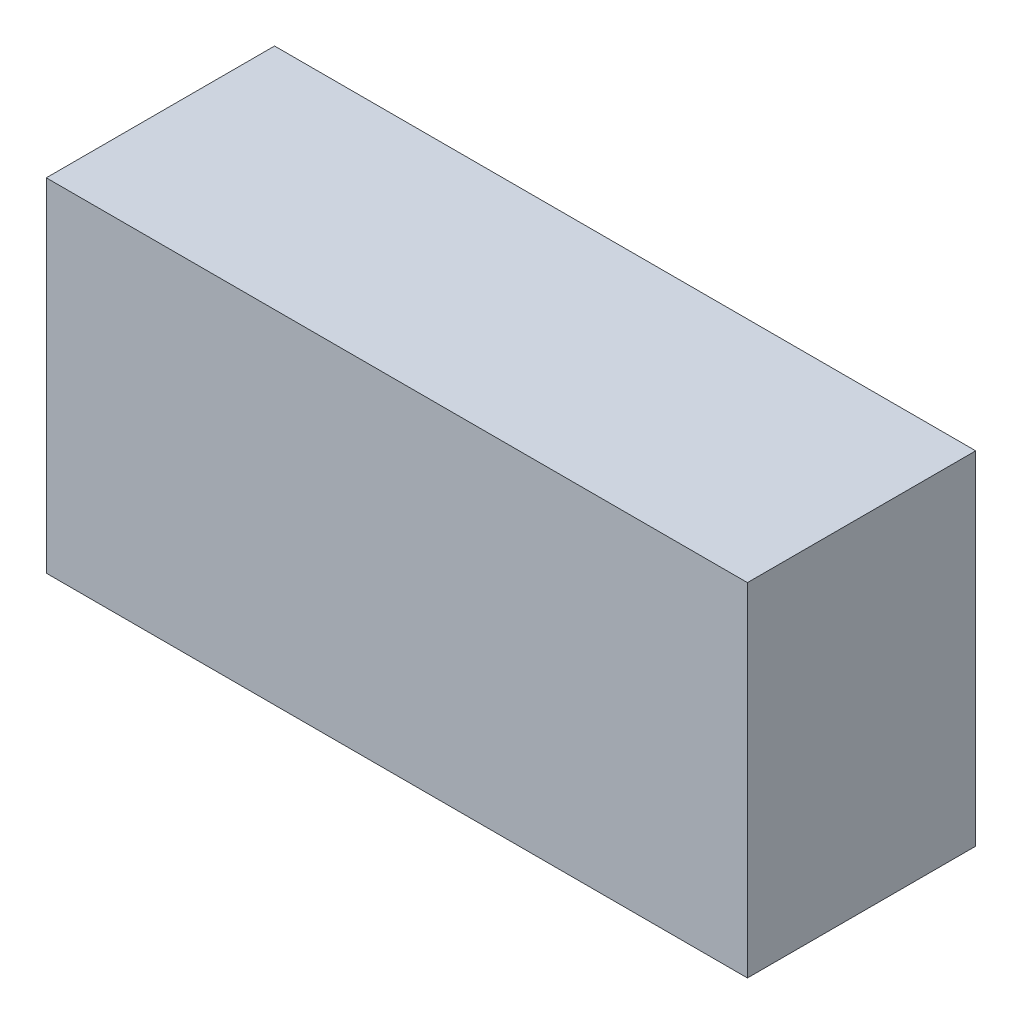
SolidWorks part; units mm, degrees
ref_plane "Alzado" through (0, 0, 0) normal (0, 0, 1) x (1, 0, 0)
ref_plane "Planta" through (0, 0, 0) normal (0, 1, 0) x (1, 0, 0)
ref_plane "Vista lateral" through (0, 0, 0) normal (1, 0, 0) x (0, 0, -1)
sketch "Croquis1" plane through (0, 0, 0) normal (0, 0, 1) x (1, 0, 0)
  line L1 (-21.5, 21) -> (21.5, 21)
  line L2 (-21.5, 21) -> (-21.5, 0)
  line L3 (-21.5, 0) -> (21.5, 0)
  line L4 (21.5, 21) -> (21.5, 0)
  dimension "D1" = 43
  dimension "D2" = 21
extrude "Saliente-Extruir1" add sketch "Croquis1" along normal blind 14
sketch "Croquis2" plane through (0, 0, 0) normal (0, 0, -1) x (-1, 0, 0)
  line L1 (-21.5, 21) -> (21.5, 21) construction
  line L3 (-21.5, 0) -> (-21.5, 21) construction
  circle A0 centre (-19.5, 19) radius 0.45
  circle A1 centre (-19.5, 2) radius 0.45
  circle A2 centre (19.5, 19) radius 0.45
  circle A3 centre (19.5, 2) radius 0.45
  dimension "D1" = 0.9
  dimension "D2" = 17
  dimension "D3" = 39
  dimension "D4" = 2
  dimension "D5" = 2
extrude "Saliente-Extruir2" add sketch "Croquis2" along normal blind 1
